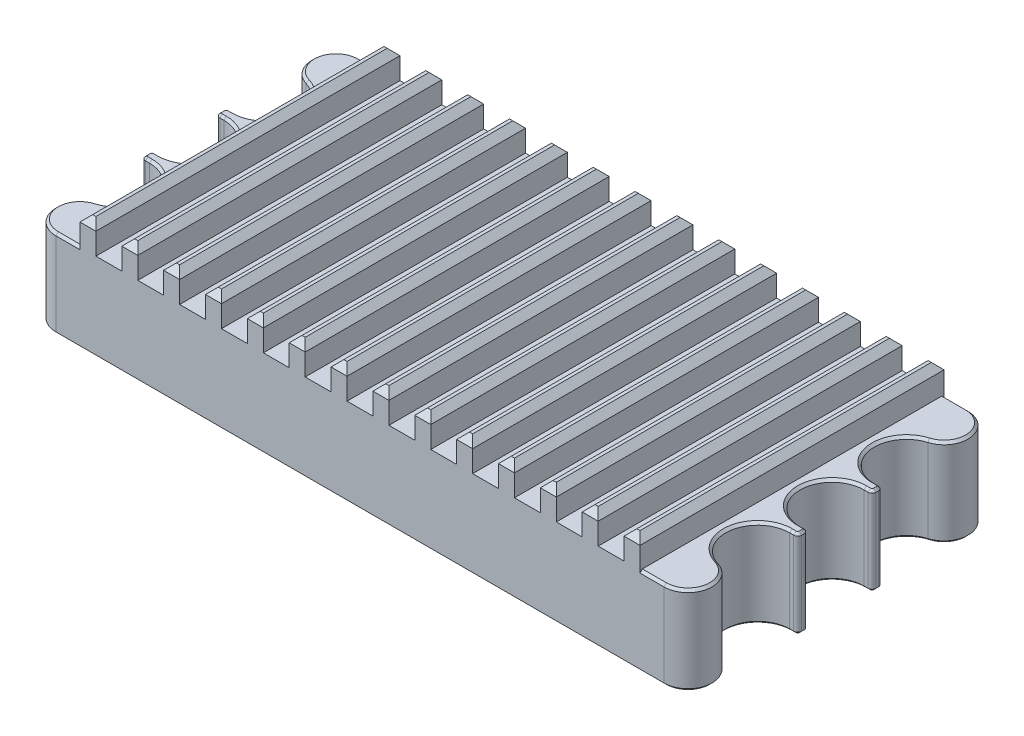
SolidWorks part; units mm, degrees
ref_plane "Front Plane" through (0, 0, 0) normal (0, 0, 1) x (1, 0, 0)
ref_plane "Top Plane" through (0, 0, 0) normal (0, 1, 0) x (1, 0, 0)
ref_plane "Right Plane" through (0, 0, 0) normal (1, 0, 0) x (0, 0, -1)
sketch "Sketch1" plane through (0, 0, 0) normal (0, 1, 0) x (1, 0, 0)
  line L0 (0, 0) -> (33, 0) construction
  line L1 (-33, 15.5) -> (33, 15.5) construction
  line L2 (-33, 15.5) -> (-33, -15.5) construction
  line L3 (-33, -15.5) -> (33, -15.5) construction
  line L4 (33, 15.5) -> (33, -15.5) construction
  line L5 (-33, 15.5) -> (33, -15.5) construction
  line L6 (-33, -15.5) -> (33, 15.5) construction
  line L7 (0, 0) -> (0, 15.5) construction
  line L8 (-35, 17.5) -> (35, 17.5)
  line L9 (35, 17.5) -> (35, -17.5)
  line L10 (-35, -17.5) -> (35, -17.5)
  line L11 (-35, 17.5) -> (-35, -17.5)
  line L12 (-36.5, 19) -> (36.5, 19)
  line L13 (36.5, 19) -> (36.5, -19)
  line L14 (-36.5, -19) -> (36.5, -19)
  line L15 (-36.5, 19) -> (-36.5, -19)
  circle A0 centre (30, 12.5) radius 1.5 construction
  circle A1 centre (30, -12.5) radius 1.5 construction
  circle A2 centre (-30, -12.5) radius 1.5 construction
  circle A3 centre (-30, 12.5) radius 1.5 construction
  point P0 (0, 0)
  dimension "D3" = 3
  dimension "D5" = 3
  dimension "D1" = 66
  dimension "D2" = 31
  dimension "D4" = 3
  dimension "D6" = 2
  dimension "D7" = 1.5
extrude "Boss-Extrude1" add sketch "Sketch1" along normal blind 1.5 contours L8 L11 L10 L9 | L12 L15 L14 L13 L11 L8 L9 L10
sketch "Sketch2" plane through (0, 0, 0) normal (0, -1, 0) x (1, 0, 0)
  line L0 (-35, 17.5) -> (35, 17.5) construction
  line L1 (-35, 17.5) -> (35, 17.5)
  line L2 (-35, 17.5) -> (-35, -17.5)
  line L3 (-35, -17.5) -> (35, -17.5)
  line L4 (35, 17.5) -> (35, -17.5)
  line L5 (-35, -17.5) -> (35, -17.5) construction
  line L6 (35, -17.5) -> (35, 17.5) construction
  line L7 (-35, -17.5) -> (-35, 17.5) construction
  line L12 (-36.5, -19) -> (36.5, -19)
  line L13 (36.5, -19) -> (36.5, 19)
  line L14 (36.5, 19) -> (-36.5, 19)
  line L15 (-36.5, 19) -> (-36.5, -19)
  line L16 (-36.5, -19) -> (36.5, -19)
  line L17 (36.5, -19) -> (36.5, 19)
  line L18 (36.5, 19) -> (-36.5, 19)
  line L19 (-36.5, 19) -> (-36.5, -19)
  dimension "D1" = 0
extrude "Boss-Extrude2" add sketch "Sketch2" along normal blind 9.5
sketch "Sketch3" plane through (0, 0, 0) normal (0, -1, 0) x (1, 0, 0)
  line L0 (35, -17.5) -> (35, 17.5) construction
  line L1 (-35, 17.5) -> (35, 17.5) construction
  line L2 (0, 0) -> (33, 0) construction
  line L3 (-35, 17.5) -> (35, 17.5)
  line L4 (-35, 17.5) -> (-35, -17.5)
  line L5 (-35, -17.5) -> (35, -17.5)
  line L6 (35, 17.5) -> (35, -17.5)
  line L7 (0, 0) -> (0, -15.5) construction
  circle A0 centre (30, 12.5) radius 2.5
  arc A1 (35, 7.2322) -> (30.8482, 10.1483) centre (31.9, 7.2322) ccw
  arc A2 (27.6483, 13.3482) -> (24.7322, 17.5) centre (24.7322, 14.4) ccw
  arc A3 (35, -7.2322) -> (30.8482, -10.1483) centre (31.9, -7.2322) cw
  circle A4 centre (30, -12.5) radius 2.5
  arc A5 (27.6483, -13.3482) -> (24.7322, -17.5) centre (24.7322, -14.4) cw
  arc A6 (-27.6483, -13.3482) -> (-24.7322, -17.5) centre (-24.7322, -14.4) ccw
  circle A7 centre (-30, -12.5) radius 2.5
  arc A8 (-35, -7.2322) -> (-30.8482, -10.1483) centre (-31.9, -7.2322) ccw
  arc A9 (-27.6483, 13.3482) -> (-24.7322, 17.5) centre (-24.7322, 14.4) cw
  arc A10 (-35, 7.2322) -> (-30.8482, 10.1483) centre (-31.9, 7.2322) cw
  circle A11 centre (-30, 12.5) radius 2.5
  line M12 (35, 17.5) -> (-35, 17.5)
  line M13 (-35, 17.5) -> (-35, -17.5)
  line M14 (-35, -17.5) -> (35, -17.5)
  line M15 (35, -17.5) -> (35, 17.5)
  dimension "D1" = 5
  dimension "D2" = 6.2
  dimension "D3" = 6.2
extrude "Boss-Extrude3" add sketch "Sketch3" along normal blind 5.5 contours A10 A11 A9 M12 M13 | A11 | A8 L4 A6 A7 M14 | A7 | A2 A0 A1 L6 M12 | A0 | A4 A5 L5 A3 M15 | A4
ref_plane "Plane1" through (0, -5.5, 0) normal (0, -1, 0) x (-1, 0, 0)
sketch "Sketch6" plane through (0, -5.5, 0) normal (0, -1, 0) x (1, 0, 0)
  line L2 (-24.7322, 17.5) -> (-35, 17.5)
  line L6 (-35, -7.2322) -> (-35, -17.5)
  line L10 (35, 7.2322) -> (35, 17.5)
  line L14 (24.7322, -17.5) -> (35, -17.5)
  line L18 (-24.7322, 17.5) -> (-35, 17.5)
  line L20 (-35, -7.2322) -> (-35, -17.5)
  line L22 (35, 7.2322) -> (35, 17.5)
  line L24 (24.7322, -17.5) -> (35, -17.5)
  line L26 (-35, 17.5) -> (-35, 7.2322)
  line L27 (-35, 17.5) -> (-35, 7.2322)
  line L28 (-35, -17.5) -> (-24.7322, -17.5)
  line L29 (-35, -17.5) -> (-24.7322, -17.5)
  line L30 (35, 17.5) -> (24.7322, 17.5)
  line L31 (35, 17.5) -> (24.7322, 17.5)
  line L32 (35, -17.5) -> (35, -7.2322)
  line L33 (35, -17.5) -> (35, -7.2322)
  arc A3 (-30.8482, 10.1483) -> (-35, 7.2322) centre (-31.9, 7.2322) ccw
  arc A4 (-30.8482, 10.1483) -> (-27.6483, 13.3482) centre (-30, 12.5) ccw
  arc A5 (-24.7322, 17.5) -> (-27.6483, 13.3482) centre (-24.7322, 14.4) ccw
  arc A6 (-30.8482, 10.1483) -> (-35, 7.2322) centre (-31.9, 7.2322) ccw
  arc A7 (-30.8482, 10.1483) -> (-27.6483, 13.3482) centre (-30, 12.5) ccw
  arc A8 (-24.7322, 17.5) -> (-27.6483, 13.3482) centre (-24.7322, 14.4) ccw
  arc A9 (-35, -7.2322) -> (-30.8482, -10.1483) centre (-31.9, -7.2322) ccw
  arc A10 (-27.6483, -13.3482) -> (-24.7322, -17.5) centre (-24.7322, -14.4) ccw
  arc A11 (-27.6483, -13.3482) -> (-30.8482, -10.1483) centre (-30, -12.5) ccw
  arc A12 (-35, -7.2322) -> (-30.8482, -10.1483) centre (-31.9, -7.2322) ccw
  arc A13 (-27.6483, -13.3482) -> (-24.7322, -17.5) centre (-24.7322, -14.4) ccw
  arc A14 (-27.6483, -13.3482) -> (-30.8482, -10.1483) centre (-30, -12.5) ccw
  arc A15 (27.6483, 13.3482) -> (24.7322, 17.5) centre (24.7322, 14.4) ccw
  arc A16 (27.6483, 13.3482) -> (30.8482, 10.1483) centre (30, 12.5) ccw
  arc A17 (35, 7.2322) -> (30.8482, 10.1483) centre (31.9, 7.2322) ccw
  arc A18 (27.6483, 13.3482) -> (24.7322, 17.5) centre (24.7322, 14.4) ccw
  arc A19 (27.6483, 13.3482) -> (30.8482, 10.1483) centre (30, 12.5) ccw
  arc A20 (35, 7.2322) -> (30.8482, 10.1483) centre (31.9, 7.2322) ccw
  arc A21 (30.8482, -10.1483) -> (35, -7.2322) centre (31.9, -7.2322) ccw
  arc A22 (30.8482, -10.1483) -> (27.6483, -13.3482) centre (30, -12.5) ccw
  arc A23 (24.7322, -17.5) -> (27.6483, -13.3482) centre (24.7322, -14.4) ccw
  arc A24 (30.8482, -10.1483) -> (35, -7.2322) centre (31.9, -7.2322) ccw
  arc A25 (30.8482, -10.1483) -> (27.6483, -13.3482) centre (30, -12.5) ccw
  arc A26 (24.7322, -17.5) -> (27.6483, -13.3482) centre (24.7322, -14.4) ccw
  dimension "D1" = 0
  dimension "D2" = 0
  dimension "D3" = 0
  dimension "D4" = 0
hole_wizard "M3 Tapped Hole1" positions "Sketch7" profile "Sketch9" tap size "M3" standard "ISO"
sketch "Sketch7" plane through (0, -5.5, 0) normal (0, -1, 0) x (-1, 0, 0)
  point P0 (30, -12.5)
  point P3 (30, 12.5)
  point P6 (-30, 12.5)
  point P9 (-30, -12.5)
sketch "Sketch9" plane through (-30, -5.5, 12.5) normal (1, 0, 0) x (0, 0, -1)
  line L0 (0, 0) -> (0, 5)
  line L1 (0, 5) -> (1.25, 4.2489)
  line L2 (1.25, 4.2489) -> (1.25, 0)
  line L5 (1.25, 0) -> (0, 0)
  line L10 (0, 5) -> (-1.25, 4.2489) construction
  line L11 (0, -6.35) -> (0, 107.95) construction
  dimension "Tap Drill Dia." = 2.5
  dimension "Tap Drill Depth" = 5
  dimension "Drill Angle" = 118
cosmetic thread "Hole Thread1" parameters "D1"=4, "D2"=3
cosmetic thread "Hole Thread2" parameters "D1"=4, "D2"=3
cosmetic thread "Hole Thread3" parameters "D1"=4, "D2"=3
cosmetic thread "Hole Thread4" parameters "D1"=4, "D2"=3
sketch "Sketch4" plane through (0, -5.5, 0) normal (0, -1, 0) x (1, 0, 0)
  line L2 (24.7322, -17.5) -> (35, -17.5)
  line L6 (24.7322, -17.5) -> (35, -17.5)
  line L8 (35, -17.5) -> (35, -7.2322)
  line L9 (35, -17.5) -> (35, -7.2322)
  arc A3 (30.8482, -10.1483) -> (35, -7.2322) centre (31.9, -7.2322) ccw
  arc A4 (30.8482, -10.1483) -> (27.6483, -13.3482) centre (30, -12.5) ccw
  arc A5 (24.7322, -17.5) -> (27.6483, -13.3482) centre (24.7322, -14.4) ccw
  arc A6 (30.8482, -10.1483) -> (35, -7.2322) centre (31.9, -7.2322) ccw
  arc A7 (30.8482, -10.1483) -> (27.6483, -13.3482) centre (30, -12.5) ccw
  arc A8 (24.7322, -17.5) -> (27.6483, -13.3482) centre (24.7322, -14.4) ccw
  dimension "D1" = 0
extrude "Cut-Extrude1" cut sketch "Sketch4" against normal blind 0.05
sketch "Sketch10" plane through (0, 0, 0) normal (0, -1, 0) x (1, 0, 0)
  line L0 (-33, -15.5) -> (33, -15.5) construction
  line L1 (-24.5, 2) -> (-7.5, 2)
  line L2 (-24.5, 2) -> (-24.5, -11)
  line L3 (-24.5, -11) -> (-7.5, -11)
  line L4 (-7.5, 2) -> (-7.5, -11)
  line L5 (-24.5, 2) -> (-7.5, -11) construction
  line L6 (-24.5, -11) -> (-7.5, 2) construction
  line L8 (-23, -9.5) -> (-9, -9.5) construction
  line L9 (-23, -9.5) -> (-23, 0.5) construction
  line L10 (-23, 0.5) -> (-9, 0.5) construction
  line L11 (-9, -9.5) -> (-9, 0.5) construction
  line L12 (35, -7.2322) -> (35, 7.2322)
  line L13 (24.7322, 17.5) -> (-24.7322, 17.5)
  line L14 (-35, 7.2322) -> (-35, -7.2322)
  line L15 (-24.7322, -17.5) -> (24.7322, -17.5)
  line L16 (35, -7.2322) -> (35, 7.2322)
  line L17 (24.7322, 17.5) -> (-24.7322, 17.5)
  line L18 (-35, 7.2322) -> (-35, -7.2322)
  line L19 (-24.7322, -17.5) -> (24.7322, -17.5)
  line L20 (-23, -9.5) -> (-9, 0.5) construction
  line L21 (-23, 0.5) -> (-9, -9.5) construction
  line L22 (-33, -15.5) -> (-33, 15.5) construction
  arc A0 (-30.6132, -10.0764) -> (-24.5, -2.2238) centre (-32.6, -2.2238) ccw
  arc A1 (-24.3051, -11) -> (-27.6483, -13.3482) centre (-24.3051, -14.5541) ccw
  arc A2 (-27.6483, -13.3482) -> (-30.8482, -10.1483) centre (-30, -12.5) ccw construction
  arc A12 (30.8482, -10.1483) -> (35, -7.2322) centre (31.9, -7.2322) ccw
  arc A13 (35, 7.2322) -> (30.8482, 10.1483) centre (31.9, 7.2322) ccw
  arc A14 (27.6483, 13.3482) -> (30.8482, 10.1483) centre (30, 12.5) ccw
  arc A15 (27.6483, 13.3482) -> (24.7322, 17.5) centre (24.7322, 14.4) ccw
  arc A16 (-24.7322, 17.5) -> (-27.6483, 13.3482) centre (-24.7322, 14.4) ccw
  arc A17 (-30.8482, 10.1483) -> (-27.6483, 13.3482) centre (-30, 12.5) ccw
  arc A18 (-30.8482, 10.1483) -> (-35, 7.2322) centre (-31.9, 7.2322) ccw
  arc A19 (-35, -7.2322) -> (-30.8482, -10.1483) centre (-31.9, -7.2322) ccw
  arc A20 (-27.6483, -13.3482) -> (-30.8482, -10.1483) centre (-30, -12.5) ccw
  arc A21 (-27.6483, -13.3482) -> (-24.7322, -17.5) centre (-24.7322, -14.4) ccw
  arc A22 (24.7322, -17.5) -> (27.6483, -13.3482) centre (24.7322, -14.4) ccw
  arc A23 (30.8482, -10.1483) -> (27.6483, -13.3482) centre (30, -12.5) ccw
  arc A24 (30.8482, -10.1483) -> (35, -7.2322) centre (31.9, -7.2322) ccw
  arc A25 (35, 7.2322) -> (30.8482, 10.1483) centre (31.9, 7.2322) ccw
  arc A26 (27.6483, 13.3482) -> (30.8482, 10.1483) centre (30, 12.5) ccw
  arc A27 (27.6483, 13.3482) -> (24.7322, 17.5) centre (24.7322, 14.4) ccw
  arc A28 (-24.7322, 17.5) -> (-27.6483, 13.3482) centre (-24.7322, 14.4) ccw
  arc A29 (-30.8482, 10.1483) -> (-27.6483, 13.3482) centre (-30, 12.5) ccw
  arc A30 (-30.8482, 10.1483) -> (-35, 7.2322) centre (-31.9, 7.2322) ccw
  arc A31 (-35, -7.2322) -> (-30.8482, -10.1483) centre (-31.9, -7.2322) ccw
  arc A32 (-27.6483, -13.3482) -> (-30.8482, -10.1483) centre (-30, -12.5) ccw
  arc A33 (-27.6483, -13.3482) -> (-24.7322, -17.5) centre (-24.7322, -14.4) ccw
  arc A34 (24.7322, -17.5) -> (27.6483, -13.3482) centre (24.7322, -14.4) ccw
  arc A35 (30.8482, -10.1483) -> (27.6483, -13.3482) centre (30, -12.5) ccw
  point P0 (-16, -4.5)
  point P5 (-16, -4.5)
  arc M16 (-30.8482, -10.1483) -> (-27.6483, -13.3482) centre (-30, -12.5) cw
  dimension "D6" = 16.2
  dimension "D7" = 10
  dimension "D1" = 1.5
  dimension "D2" = 1.5
  dimension "D3" = 14
  dimension "D4" = 6
  dimension "D8" = 10
  dimension "D5" = 0
extrude "Boss-Extrude4" add sketch "Sketch10" along normal blind 2.4 contours A1 L3 L2 A0 M16 | L4 L1 L2 L3
fillet "Fillet1" radius 1 3 edges at (-24.5, -1.2, 2) (-7.5, -1.2, 2) (-7.5, -1.2, -11)
sketch "Sketch11" plane through (0, -9.5, 0) normal (0, -1, 0) x (1, 0, 0)
  line L1 (-36.5, 19) -> (-41, 19)
  line L2 (-36.5, 19) -> (-36.5, -19)
  line L3 (-36.5, -19) -> (-41, -19)
  line L4 (-36.5, 19) -> (-36.5, -19)
  line L5 (-36.5, -19) -> (36.5, -19)
  line L6 (36.5, -19) -> (36.5, 19)
  line L7 (36.5, 19) -> (-36.5, 19)
  line L8 (-36.5, 19) -> (-36.5, -19)
  line L9 (-36.5, -19) -> (36.5, -19)
  line L10 (36.5, -19) -> (36.5, 19)
  line L11 (36.5, 19) -> (-36.5, 19)
  line L12 (-41, 19) -> (-41, -19)
  line L13 (36.5, 19) -> (41, 19)
  line L14 (36.5, 19) -> (36.5, -19)
  line L15 (36.5, -19) -> (41, -19)
  line L16 (41, 19) -> (41, -19)
  line M13 (-36.5, 19) -> (-36.5, -19)
  line M15 (36.5, -19) -> (36.5, 19)
  dimension "D2" = 4.5
  dimension "D3" = 4.5
  dimension "D1" = 0
extrude "Boss-Extrude5" add sketch "Sketch11" against normal up to surface (11 mm away) contours L1 L12 L3 M13 | L16 L13 L15 M15 up to face at (0, 1.5, 0)
sketch "Sketch12" plane through (0, -9.5, 0) normal (0, -1, 0) x (1, 0, 0)
  line L0 (38, 19) -> (38, -19) construction
  line L1 (41, 19) -> (-41, 19) construction
  line L2 (-41, -19) -> (41, -19) construction
  line L3 (41, 19) -> (41, -19) construction
  line L4 (35, -17.5) -> (35, 17.5) construction
  line L5 (0, 0) -> (40, 0) construction
  line L6 (40, 9.2918) -> (40, -19) construction
  line L7 (40, -4) -> (41, -4)
  line L8 (40, -5.2918) -> (41, -5.2918)
  line L9 (41, 19) -> (-41, 19)
  line L10 (-41, 19) -> (-41, -19)
  line L11 (-41, -19) -> (41, -19)
  line L12 (41, -19) -> (41, 19)
  line L13 (41, 19) -> (-41, 19)
  line L14 (-41, 19) -> (-41, -19)
  line L15 (-41, -19) -> (41, -19)
  line L16 (41, -19) -> (41, 19)
  line L17 (40, 4) -> (41, 4)
  line L18 (40, 5.2918) -> (41, 5.2918)
  line L19 (0, 0) -> (0, 17.5) construction
  line L20 (24.7322, 17.5) -> (-24.7322, 17.5) construction
  line L21 (-40, -5.2918) -> (-41, -5.2918)
  line L22 (-40, -4) -> (-41, -4)
  line L23 (-40, 4) -> (-41, 4)
  line L24 (-40, 5.2918) -> (-41, 5.2918)
  line L25 (-38, 19) -> (-38, -19) construction
  circle A0 centre (38, 16) radius 3
  arc A1 (38.8571, 13.1251) -> (40, 5.2918) centre (40, 9.2918) ccw
  circle A2 centre (38, -16) radius 3
  arc A3 (40, 4) -> (40, -4) centre (40, 0) ccw
  arc A4 (40, -5.2918) -> (38.8571, -13.1251) centre (40, -9.2918) ccw
  circle A6 centre (-38, -16) radius 3
  arc A7 (-40, -5.2918) -> (-38.8571, -13.1251) centre (-40, -9.2918) cw
  arc A8 (-40, 4) -> (-40, -4) centre (-40, 0) cw
  arc A9 (-38.8571, 13.1251) -> (-40, 5.2918) centre (-40, 9.2918) cw
  circle A10 centre (-38, 16) radius 3
  point P16 (36, 9.2918)
  point P24 (40, 5.2918)
  point P27 (40, -5.2918)
  line M2 (41, 19) -> (-41, 19)
  line M3 (-41, 19) -> (-41, -19)
  line M4 (-41, -19) -> (41, -19)
  line M5 (41, -19) -> (41, 19)
  dimension "D2" = 0
  dimension "D3" = 1
  dimension "D4" = 8
  dimension "D5" = 8
  dimension "D6" = 8
  dimension "D1" = 3
extrude "Cut-Extrude2" cut sketch "Sketch12" against normal up to surface (11 mm away) contours A0 L16 M2 | A0 A1 L18 M5 | L17 A3 L7 M5 | L8 A4 A2 L16 | A2 L15 M5 | A6 M4 M3 | A7 L21 L14 A6 | A8 L23 L14 L22 | A9 A10 L14 L24 | A10 M3 M2 up to face at (0, 1.5, 0)
fillet "Fillet2" radius 0.5 8 edges at (-41, -4, 5.2918) (-41, -4, 4) (-41, -4, -4) (-41, -4, -5.2918) (41, -4, -4) (41, -4, -5.2918) (41, -4, 5.2918) (41, -4, 4)
sketch "Sketch13" plane through (0, -9.5, 0) normal (0, -1, 0) x (1, 0, 0)
  line L14 (-40, 5.2918) -> (-40.5, 5.2918)
  line L15 (-41, 4.7918) -> (-41, 4.5)
  line L16 (-40.5, 4) -> (-40, 4)
  line L17 (-40, -4) -> (-40.5, -4)
  line L18 (-41, -4.5) -> (-41, -4.7918)
  line L19 (-40.5, -5.2918) -> (-40, -5.2918)
  line L20 (-38, -19) -> (38, -19)
  line L21 (40, -5.2918) -> (40.5, -5.2918)
  line L22 (41, -4.7918) -> (41, -4.5)
  line L23 (40.5, -4) -> (40, -4)
  line L24 (40, 4) -> (40.5, 4)
  line L25 (41, 4.5) -> (41, 4.7918)
  line L26 (40.5, 5.2918) -> (40, 5.2918)
  line L27 (38, 19) -> (-38, 19)
  line L28 (-40, 5.2918) -> (-40.5, 5.2918)
  line L29 (-41, 4.7918) -> (-41, 4.5)
  line L30 (-40.5, 4) -> (-40, 4)
  line L31 (-40, -4) -> (-40.5, -4)
  line L32 (-41, -4.5) -> (-41, -4.7918)
  line L33 (-40.5, -5.2918) -> (-40, -5.2918)
  line L34 (-38, -19) -> (38, -19)
  line L35 (40, -5.2918) -> (40.5, -5.2918)
  line L36 (41, -4.7918) -> (41, -4.5)
  line L37 (40.5, -4) -> (40, -4)
  line L38 (40, 4) -> (40.5, 4)
  line L39 (41, 4.5) -> (41, 4.7918)
  line L40 (40.5, 5.2918) -> (40, 5.2918)
  line L41 (38, 19) -> (-38, 19)
  arc A18 (-40.5, 5.2918) -> (-41, 4.7918) centre (-40.5, 4.7918) ccw
  arc A19 (-41, 4.5) -> (-40.5, 4) centre (-40.5, 4.5) ccw
  arc A20 (-40, -4) -> (-40, 4) centre (-40, 0) ccw
  arc A21 (-40.5, -4) -> (-41, -4.5) centre (-40.5, -4.5) ccw
  arc A22 (-41, -4.7918) -> (-40.5, -5.2918) centre (-40.5, -4.7918) ccw
  arc A23 (-38.8571, -13.1251) -> (-40, -5.2918) centre (-40, -9.2918) ccw
  arc A24 (-38.8571, -13.1251) -> (-38, -19) centre (-38, -16) ccw
  arc A25 (38, -19) -> (38.8571, -13.1251) centre (38, -16) ccw
  arc A26 (40, -5.2918) -> (38.8571, -13.1251) centre (40, -9.2918) ccw
  arc A27 (40.5, -5.2918) -> (41, -4.7918) centre (40.5, -4.7918) ccw
  arc A28 (41, -4.5) -> (40.5, -4) centre (40.5, -4.5) ccw
  arc A29 (40, 4) -> (40, -4) centre (40, 0) ccw
  arc A30 (40.5, 4) -> (41, 4.5) centre (40.5, 4.5) ccw
  arc A31 (41, 4.7918) -> (40.5, 5.2918) centre (40.5, 4.7918) ccw
  arc A32 (38.8571, 13.1251) -> (40, 5.2918) centre (40, 9.2918) ccw
  arc A33 (38.8571, 13.1251) -> (38, 19) centre (38, 16) ccw
  arc A34 (-38, 19) -> (-38.8571, 13.1251) centre (-38, 16) ccw
  arc A35 (-40, 5.2918) -> (-38.8571, 13.1251) centre (-40, 9.2918) ccw
  arc A36 (-40.5, 5.2918) -> (-41, 4.7918) centre (-40.5, 4.7918) ccw
  arc A37 (-41, 4.5) -> (-40.5, 4) centre (-40.5, 4.5) ccw
  arc A38 (-40, -4) -> (-40, 4) centre (-40, 0) ccw
  arc A39 (-40.5, -4) -> (-41, -4.5) centre (-40.5, -4.5) ccw
  arc A40 (-41, -4.7918) -> (-40.5, -5.2918) centre (-40.5, -4.7918) ccw
  arc A41 (-38.8571, -13.1251) -> (-40, -5.2918) centre (-40, -9.2918) ccw
  arc A42 (-38.8571, -13.1251) -> (-38, -19) centre (-38, -16) ccw
  arc A43 (38, -19) -> (38.8571, -13.1251) centre (38, -16) ccw
  arc A44 (40, -5.2918) -> (38.8571, -13.1251) centre (40, -9.2918) ccw
  arc A45 (40.5, -5.2918) -> (41, -4.7918) centre (40.5, -4.7918) ccw
  arc A46 (41, -4.5) -> (40.5, -4) centre (40.5, -4.5) ccw
  arc A47 (40, 4) -> (40, -4) centre (40, 0) ccw
  arc A48 (40.5, 4) -> (41, 4.5) centre (40.5, 4.5) ccw
  arc A49 (41, 4.7918) -> (40.5, 5.2918) centre (40.5, 4.7918) ccw
  arc A50 (38.8571, 13.1251) -> (40, 5.2918) centre (40, 9.2918) ccw
  arc A51 (38.8571, 13.1251) -> (38, 19) centre (38, 16) ccw
  arc A52 (-38, 19) -> (-38.8571, 13.1251) centre (-38, 16) ccw
  arc A53 (-40, 5.2918) -> (-38.8571, 13.1251) centre (-40, 9.2918) ccw
  dimension "D1" = 0
hole_wizard "M3 Tapped Hole2" positions "3DSketch1" profile "Sketch14" tap size "M3" standard "ISO"
sketch3d "3DSketch1"
  point P0 (38, -9.5, 16)
  point P3 (38, -9.5, -16)
  point P6 (-38, -9.5, -16)
  point P9 (-38, -9.5, 16)
sketch "Sketch14" plane through (38, -9.5, 16) normal (1, 0, 0) x (0, 0, -1)
  line L0 (0, 0) -> (0, 7.5)
  line L1 (0, 7.5) -> (1.25, 6.7489)
  line L2 (1.25, 6.7489) -> (1.25, 0)
  line L5 (1.25, 0) -> (0, 0)
  line L10 (0, 7.5) -> (-1.25, 6.7489) construction
  line L11 (0, -6.35) -> (0, 107.95) construction
  dimension "Tap Drill Dia." = 2.5
  dimension "Tap Drill Depth" = 7.5
  dimension "Drill Angle" = 118
cosmetic thread "Hole Thread5" parameters "D1"=6, "D2"=3
cosmetic thread "Hole Thread6" parameters "D1"=6, "D2"=3
cosmetic thread "Hole Thread7" parameters "D1"=6, "D2"=3
cosmetic thread "Hole Thread8" parameters "D1"=6, "D2"=3
sketch "Sketch15" plane through (0, 1.5, 0) normal (0, 1, 0) x (1, 0, 0)
  line L0 (-35, 19) -> (-35, -19)
  line L1 (-38, 19) -> (38, 19) construction
  line L2 (-38, -19) -> (38, -19) construction
  line L3 (35, 19) -> (35, -19)
  line L4 (29.7692, 19) -> (29.7692, -19)
  line L5 (35, 19) -> (33, 19)
  line L6 (35, 19) -> (35, -19)
  line L7 (35, -19) -> (33, -19)
  line L8 (33, 19) -> (33, -19)
  line L9 (29.7692, 19) -> (27.7692, 19)
  line L10 (27.7692, 19) -> (27.7692, -19)
  line L11 (29.7692, -19) -> (27.7692, -19)
  line L12 (24.5385, 19) -> (24.5385, -19)
  line L13 (24.5385, 19) -> (22.5385, 19)
  line L14 (22.5385, 19) -> (22.5385, -19)
  line L15 (24.5385, -19) -> (22.5385, -19)
  line L16 (19.3077, 19) -> (19.3077, -19)
  line L17 (19.3077, 19) -> (17.3077, 19)
  line L18 (-41, -4.5) -> (-41, -4.7918)
  line L19 (-40.5, -5.2918) -> (-40, -5.2918)
  line L20 (-38, -19) -> (38, -19)
  line L21 (40, -5.2918) -> (40.5, -5.2918)
  line L22 (41, -4.7918) -> (41, -4.5)
  line L23 (40.5, -4) -> (40, -4)
  line L24 (40, 4) -> (40.5, 4)
  line L25 (41, 4.5) -> (41, 4.7918)
  line L26 (40.5, 5.2918) -> (40, 5.2918)
  line L27 (38, 19) -> (-38, 19)
  line L28 (-40, 5.2918) -> (-40.5, 5.2918)
  line L29 (-41, 4.7918) -> (-41, 4.5)
  line L30 (-40.5, 4) -> (-40, 4)
  line L31 (-40, -4) -> (-40.5, -4)
  line L32 (-41, -4.5) -> (-41, -4.7918)
  line L33 (-40.5, -5.2918) -> (-40, -5.2918)
  line L34 (-38, -19) -> (38, -19)
  line L35 (40, -5.2918) -> (40.5, -5.2918)
  line L36 (41, -4.7918) -> (41, -4.5)
  line L37 (40.5, -4) -> (40, -4)
  line L38 (40, 4) -> (40.5, 4)
  line L39 (41, 4.5) -> (41, 4.7918)
  line L40 (40.5, 5.2918) -> (40, 5.2918)
  line L41 (38, 19) -> (-38, 19)
  line L42 (-40, 5.2918) -> (-40.5, 5.2918)
  line L43 (-41, 4.7918) -> (-41, 4.5)
  line L44 (-40.5, 4) -> (-40, 4)
  line L45 (-40, -4) -> (-40.5, -4)
  line L46 (17.3077, 19) -> (17.3077, -19)
  line L47 (19.3077, -19) -> (17.3077, -19)
  line L48 (14.0769, 19) -> (14.0769, -19)
  line L49 (14.0769, 19) -> (12.0769, 19)
  line L50 (12.0769, 19) -> (12.0769, -19)
  line L51 (14.0769, -19) -> (12.0769, -19)
  line L52 (8.8462, 19) -> (8.8462, -19)
  line L53 (8.8462, 19) -> (6.8462, 19)
  line L54 (6.8462, 19) -> (6.8462, -19)
  line L55 (8.8462, -19) -> (6.8462, -19)
  line L56 (3.6154, 19) -> (3.6154, -19)
  line L57 (3.6154, 19) -> (1.6154, 19)
  line L58 (1.6154, 19) -> (1.6154, -19)
  line L59 (3.6154, -19) -> (1.6154, -19)
  line L60 (-1.6154, 19) -> (-1.6154, -19)
  line L61 (-1.6154, 19) -> (-3.6154, 19)
  line L62 (-3.6154, 19) -> (-3.6154, -19)
  line L63 (-1.6154, -19) -> (-3.6154, -19)
  line L64 (-6.8462, 19) -> (-6.8462, -19)
  line L65 (-6.8462, 19) -> (-8.8462, 19)
  line L66 (-8.8462, 19) -> (-8.8462, -19)
  line L67 (-6.8462, -19) -> (-8.8462, -19)
  line L68 (-12.0769, 19) -> (-12.0769, -19)
  line L69 (-12.0769, 19) -> (-14.0769, 19)
  line L70 (-14.0769, 19) -> (-14.0769, -19)
  line L71 (-12.0769, -19) -> (-14.0769, -19)
  line L72 (-17.3077, 19) -> (-17.3077, -19)
  line L73 (-17.3077, 19) -> (-19.3077, 19)
  line L74 (-19.3077, 19) -> (-19.3077, -19)
  line L75 (-17.3077, -19) -> (-19.3077, -19)
  line L76 (-22.5385, 19) -> (-22.5385, -19)
  line L77 (-22.5385, 19) -> (-24.5385, 19)
  line L78 (-24.5385, 19) -> (-24.5385, -19)
  line L79 (-22.5385, -19) -> (-24.5385, -19)
  line L80 (-27.7692, 19) -> (-27.7692, -19)
  line L81 (-27.7692, 19) -> (-29.7692, 19)
  line L82 (-29.7692, 19) -> (-29.7692, -19)
  line L83 (-27.7692, -19) -> (-29.7692, -19)
  line L84 (-33, 19) -> (-33, -19)
  line L85 (-33, 19) -> (-35, 19)
  line L86 (-35, 19) -> (-35, -19)
  line L87 (-33, -19) -> (-35, -19)
  arc A18 (-41, -4.7918) -> (-40.5, -5.2918) centre (-40.5, -4.7918) ccw
  arc A19 (-38.8571, -13.1251) -> (-40, -5.2918) centre (-40, -9.2918) ccw
  arc A20 (-38.8571, -13.1251) -> (-38, -19) centre (-38, -16) ccw
  arc A21 (38, -19) -> (38.8571, -13.1251) centre (38, -16) ccw
  arc A22 (40, -5.2918) -> (38.8571, -13.1251) centre (40, -9.2918) ccw
  arc A23 (40.5, -5.2918) -> (41, -4.7918) centre (40.5, -4.7918) ccw
  arc A24 (41, -4.5) -> (40.5, -4) centre (40.5, -4.5) ccw
  arc A25 (40, 4) -> (40, -4) centre (40, 0) ccw
  arc A26 (40.5, 4) -> (41, 4.5) centre (40.5, 4.5) ccw
  arc A27 (41, 4.7918) -> (40.5, 5.2918) centre (40.5, 4.7918) ccw
  arc A28 (38.8571, 13.1251) -> (40, 5.2918) centre (40, 9.2918) ccw
  arc A29 (38.8571, 13.1251) -> (38, 19) centre (38, 16) ccw
  arc A30 (-38, 19) -> (-38.8571, 13.1251) centre (-38, 16) ccw
  arc A31 (-40, 5.2918) -> (-38.8571, 13.1251) centre (-40, 9.2918) ccw
  arc A32 (-40.5, 5.2918) -> (-41, 4.7918) centre (-40.5, 4.7918) ccw
  arc A33 (-41, 4.5) -> (-40.5, 4) centre (-40.5, 4.5) ccw
  arc A34 (-40, -4) -> (-40, 4) centre (-40, 0) ccw
  arc A35 (-40.5, -4) -> (-41, -4.5) centre (-40.5, -4.5) ccw
  arc A36 (-41, -4.7918) -> (-40.5, -5.2918) centre (-40.5, -4.7918) ccw
  arc A37 (-38.8571, -13.1251) -> (-40, -5.2918) centre (-40, -9.2918) ccw
  arc A38 (-38.8571, -13.1251) -> (-38, -19) centre (-38, -16) ccw
  arc A39 (38, -19) -> (38.8571, -13.1251) centre (38, -16) ccw
  arc A40 (40, -5.2918) -> (38.8571, -13.1251) centre (40, -9.2918) ccw
  arc A41 (40.5, -5.2918) -> (41, -4.7918) centre (40.5, -4.7918) ccw
  arc A42 (41, -4.5) -> (40.5, -4) centre (40.5, -4.5) ccw
  arc A43 (40, 4) -> (40, -4) centre (40, 0) ccw
  arc A44 (40.5, 4) -> (41, 4.5) centre (40.5, 4.5) ccw
  arc A45 (41, 4.7918) -> (40.5, 5.2918) centre (40.5, 4.7918) ccw
  arc A46 (38.8571, 13.1251) -> (40, 5.2918) centre (40, 9.2918) ccw
  arc A47 (38.8571, 13.1251) -> (38, 19) centre (38, 16) ccw
  arc A48 (-38, 19) -> (-38.8571, 13.1251) centre (-38, 16) ccw
  arc A49 (-40, 5.2918) -> (-38.8571, 13.1251) centre (-40, 9.2918) ccw
  arc A50 (-40.5, 5.2918) -> (-41, 4.7918) centre (-40.5, 4.7918) ccw
  arc A51 (-41, 4.5) -> (-40.5, 4) centre (-40.5, 4.5) ccw
  arc A52 (-40, -4) -> (-40, 4) centre (-40, 0) ccw
  arc A53 (-40.5, -4) -> (-41, -4.5) centre (-40.5, -4.5) ccw
  line M72 (-38, -19) -> (38, -19)
  line M88 (38, 19) -> (-38, 19)
  dimension "D1" = 0
  dimension "D2" = 70
  dimension "D3" = 35
  dimension "D4" = 2
  dimension "D5" = 14
extrude "Boss-Extrude6" add sketch "Sketch15" along normal blind 3.5 contours L8 L3 M88 M72 | L10 L4 M88 M72 | L14 L12 M88 M72 | L46 L34 L16 M88 | L41 L50 L34 L48 | L41 L54 L34 L52 | L41 L66 L34 L64 | L41 L70 L34 L68 | L41 L74 L34 L72 | L84 L41 L0 M72 | L56 L59 L58 L57 | L60 L63 L62 L61 | L76 L79 L78 L77 | L80 L83 L82 L81
chamfer "Chamfer1" distance 0.8 angle 45 56 edges at (-34, 5, -19) (-34, 5, 19) (-35, 5, 0) (-33, 5, 0) (-27.7692, 5, 0) (-28.7692, 5, -19) (-28.7692, 5, 19) (-29.7692, 5, 0) (-22.5385, 5, 0) (-23.5385, 5, -19) (-23.5385, 5, 19) (-24.5385, 5, 0) (-17.3077, 5, 0) (-18.3077, 5, -19) (-18.3077, 5, 19) (-19.3077, 5, 0) (-12.0769, 5, 0) (-13.0769, 5, -19) (-13.0769, 5, 19) (-14.0769, 5, 0) (-6.8462, 5, 0) (-7.8462, 5, -19) (-7.8462, 5, 19) (-8.8462, 5, 0) (-1.6154, 5, 0) (-2.6154, 5, -19) (-2.6154, 5, 19) (-3.6154, 5, 0) (3.6154, 5, 0) (2.6154, 5, -19) (2.6154, 5, 19) (1.6154, 5, 0) (8.8462, 5, 0) (7.8462, 5, -19) (7.8462, 5, 19) (6.8462, 5, 0) (14.0769, 5, 0) (13.0769, 5, -19) (13.0769, 5, 19) (12.0769, 5, 0) (19.3077, 5, 0) (18.3077, 5, -19) (18.3077, 5, 19) (17.3077, 5, 0) (24.5385, 5, 0) (23.5385, 5, -19) (23.5385, 5, 19) (22.5385, 5, 0) (29.7692, 5, 0) (28.7692, 5, -19) (28.7692, 5, 19) (27.7692, 5, 0) (35, 5, 0) (34, 5, -19) (34, 5, 19) (33, 5, 0)
fillet "Fillet3" radius 3.1 4 edges at (-35, -7.5, -17.5) (-35, -7.5, 17.5) (35, -7.475, -17.5) (35, -7.5, 17.5)
chamfer "Chamfer2" distance 0.3 angle 45 74 edges at (-35, -9.5, 0) (0, -9.5, -17.5) (0, -9.5, 17.5) (35, -9.5, 0) (-34.092, -9.5, -16.592) (-34.092, -9.5, 16.592) (34.092, -9.5, -16.592) (34.092, -9.5, 16.592) (0, -9.5, 19) (0, -9.5, -19) (-36.5, 1.5, -19) (-36.5, 1.5, 19) (-40.9686, -9.5, 16.4331) (-40.9686, 1.5, 16.4331) (-40.9686, -9.5, -16.4331) (-40.9686, 1.5, -16.4331) (40.9686, 1.5, -16.4331) (40.9686, -9.5, -16.4331) (40.9686, 1.5, 16.4331) (40.9686, -9.5, 16.4331) (36.0419, -9.5, 8.7143) (40.25, -9.5, 5.2918) (36.0419, 1.5, 8.7143) (40.25, 1.5, 5.2918) (40.25, 1.5, 4) (36, -9.5, 0) (40.25, -9.5, -4) (36, 1.5, 0) (40.25, 1.5, -4) (40.25, -9.5, 4) (40.25, 1.5, -5.2918) (36.0419, -9.5, -8.7143) (36.0419, 1.5, -8.7143) (40.25, -9.5, -5.2918) (-36.0419, 1.5, -8.7143) (-40.25, -9.5, -5.2918) (-40.25, 1.5, -5.2918) (-36.0419, -9.5, -8.7143) (-36, 1.5, 0) (-40.25, 1.5, -4) (-40.25, -9.5, 4) (-40.25, 1.5, 4) (-40.25, -9.5, -4) (-36, -9.5, 0) (-36.0419, 1.5, 8.7143) (-40.25, 1.5, 5.2918) (-40.25, -9.5, 5.2918) (-36.0419, -9.5, 8.7143) (41, -9.5, -4.6459) (41, -9.5, 4.6459) (-41, -9.5, 4.6459) (-41, -9.5, -4.6459) (40.8536, -9.5, 4.1464) (40.8536, -9.5, 5.1453) (40.8536, -9.5, -5.1453) (40.8536, -9.5, -4.1464) (-40.8536, -9.5, -5.1453) (-40.8536, -9.5, -4.1464) (-40.8536, -9.5, 4.1464) (-40.8536, -9.5, 5.1453) (-41, 1.5, 4.6459) (-41, 1.5, -4.6459) (41, 1.5, 4.6459) (41, 1.5, -4.6459) (40.8536, 1.5, 4.1464) (40.8536, 1.5, 5.1453) (40.8536, 1.5, -5.1453) (40.8536, 1.5, -4.1464) (-40.8536, 1.5, -5.1453) (-40.8536, 1.5, -4.1464) (-40.8536, 1.5, 4.1464) (-40.8536, 1.5, 5.1453) (36.5, 1.5, 19) (36.5, 1.5, -19)
chamfer "Chamfer3" distance 0.3 angle 45 21 edges at (33.6818, -5.45, -9.769) (27.269, -5.45, -16.1818) (28.2322, -5.45, -10.7322) (27.269, -5.5, 16.1818) (33.6818, -5.5, 9.769) (28.2322, -5.5, 10.7322) (-26.3478, -2.4, -11.6457) (-16.4025, -2.4, -11) (-7.7929, -2.4, -10.7071) (-7.5, -2.4, -4.5) (-7.7929, -2.4, 1.7071) (-16, -2.4, 2) (-24.2071, -2.4, 1.7071) (-24.5, -2.4, -0.6119) (-26.2085, -2.4, -7.1996) (-27.269, -5.5, -16.1818) (-33.6818, -5.5, -9.769) (-28.2322, -5.5, -10.7322) (-27.269, -5.5, 16.1818) (-28.2322, -5.5, 10.7322) (-33.6818, -5.5, 9.769)
sketch "info text" plane through (0, 0, -19) normal (0, 0, -1) x (-1, 0, 0)
  text T0 "9V-36V IN   5V10A OUT"
sketch "Sketch18" plane through (0, 0, 19) normal (0, 0, 1) x (1, 0, 0)
  line L0 (-34.0276, -5.4132) -> (15.9705, -4.9715) construction
  dimension "D1" = 50
